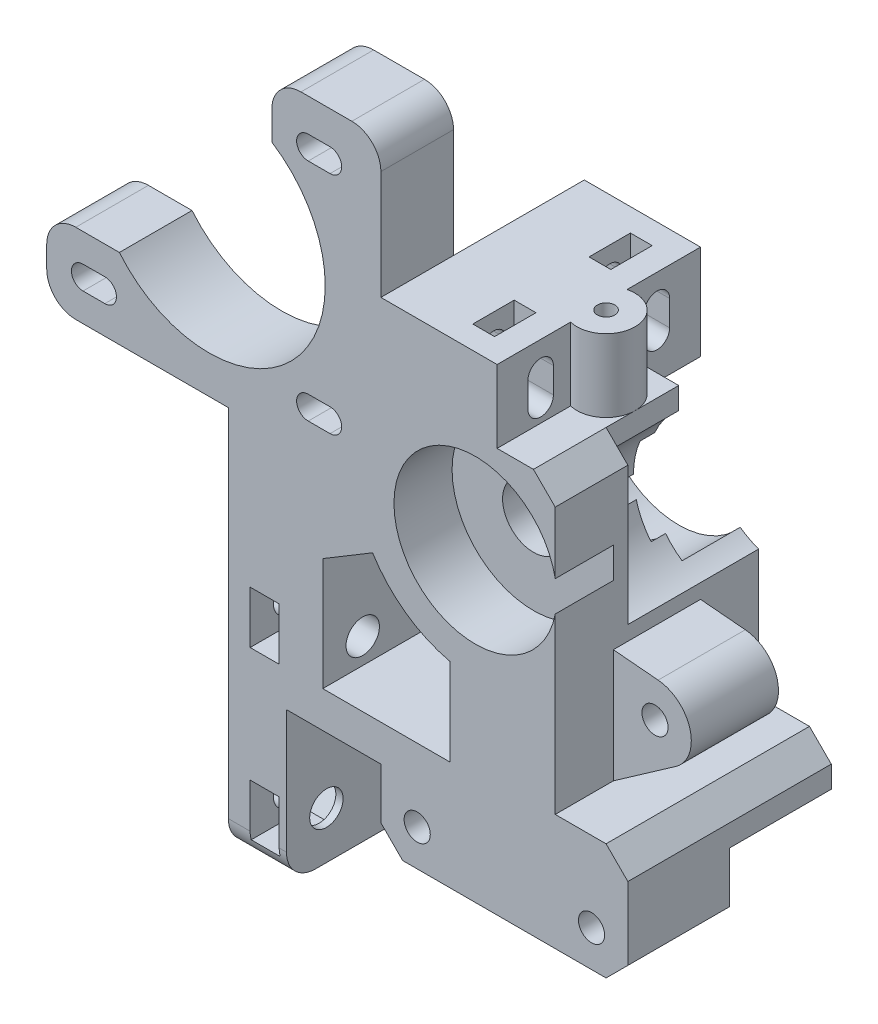
SolidWorks part; units mm, degrees
ref_plane "Front Plane" through (0, 0, 0) normal (0, 0, 1) x (1, 0, 0)
ref_plane "Top Plane" through (0, 0, 0) normal (0, 1, 0) x (1, 0, 0)
ref_plane "Right Plane" through (0, 0, 0) normal (1, 0, 0) x (0, 0, -1)
sketch "Sketch1" plane through (0, 0, 0) normal (0, 0, 1) x (1, 0, 0)
  line L0 (0, 0) -> (0, -11)
  line L1 (0, -11) -> (25, -11)
  line L2 (25, -11) -> (25, -64)
  line L3 (25, -64) -> (33, -64)
  line L4 (33, -64) -> (33, -43)
  line L5 (33, -43) -> (46, -43)
  line L6 (46, -43) -> (46, -53)
  line L7 (46, -53) -> (85, -53)
  line L8 (85, -53) -> (85, -43) construction
  line L9 (85, -43) -> (80, -43)
  line L10 (80, -43) -> (80, -37)
  line L11 (80, -37) -> (70, -37)
  line L12 (70, -37) -> (78.6011, -30.9774)
  line L13 (70, -37) -> (70, -21.361) construction
  line L14 (70, -21.361) -> (76.169, -21.9007)
  line L15 (70, -21.361) -> (70, 12.639)
  line L16 (70, 12.639) -> (46, 12.639)
  line L17 (46, 12.639) -> (46, 31.639)
  line L18 (46, 31.639) -> (31, 31.639)
  line L19 (31, 31.639) -> (31, 23.639)
  line L20 (0, 0) -> (10, 0)
  line L21 (38, -22.5) -> (38, -38)
  line L22 (38, -38) -> (55.5, -38)
  line L23 (55.5, -38) -> (55.5, -26)
  line L24 (38, -22.5) -> (44.8573, -18.3797)
  line L25 (85, -48) -> (46, -48) construction
  line L26 (25, -11) -> (59, -11) construction
  line L27 (5, -5.5) -> (8, -5.5) construction
  line L28 (5, -3.9) -> (8, -3.9)
  line L29 (5, -7.1) -> (8, -7.1)
  line L30 (36, -5.5) -> (39, -5.5) construction
  line L31 (36, -3.9) -> (39, -3.9)
  line L32 (36, -7.1) -> (39, -7.1)
  line L33 (36, 25.5) -> (39, 25.5) construction
  line L34 (36, 27.1) -> (39, 27.1)
  line L35 (36, 23.9) -> (39, 23.9)
  line L36 (5, -5.5) -> (36, -5.5) construction
  line L37 (36, -5.5) -> (36, 25.5) construction
  line L38 (5, -5.5) -> (0, -5.5) construction
  arc A0 (85, -53) -> (85, -43) centre (85, -48) ccw
  circle A1 centre (75.7332, -26.8817) radius 5
  arc A2 (10, 0) -> (31, 23.639) centre (22.3388, 10.186) ccw
  arc A3 (44.8573, -18.3797) -> (55.5, -26) centre (59.3127, -9.4331) ccw
  circle A4 centre (51, -48) radius 1.8
  circle A5 centre (75, -48) radius 1.8
  circle A6 centre (85, -48) radius 1.8
  circle A7 centre (75.7332, -26.8817) radius 1.8
  circle A8 centre (59, -11) radius 4.25
  arc A9 (5, -3.9) -> (5, -7.1) centre (5, -5.5) ccw
  arc A10 (8, -7.1) -> (8, -3.9) centre (8, -5.5) ccw
  arc A11 (36, -3.9) -> (36, -7.1) centre (36, -5.5) ccw
  arc A12 (39, -7.1) -> (39, -3.9) centre (39, -5.5) ccw
  arc A13 (36, 27.1) -> (36, 23.9) centre (36, 25.5) ccw
  arc A14 (39, 23.9) -> (39, 27.1) centre (39, 25.5) ccw
  point P45 (6.5, -5.5)
  point P50 (37.5, -5.5)
  point P57 (37.5, 25.5)
  dimension "D1" = 11
  dimension "D14" = 35
  dimension "D9" = 10
  dimension "D15" = 10
  dimension "D21" = 10
  dimension "D28" = 17
  dimension "D31" = 3.6
  dimension "D33" = 24
  dimension "D34" = 34
  dimension "D35" = 8.5
  dimension "D37" = 1.6
  dimension "D39" = 5
  dimension "D40" = 16
  dimension "D2" = 25
  dimension "D4" = 8
  dimension "D5" = 21
  dimension "D6" = 13
  dimension "D7" = 10
  dimension "D8" = 39
  dimension "D10" = 5
  dimension "D11" = 6
  dimension "D12" = 10
  dimension "D13" = 10.5
  dimension "D16" = 40
  dimension "D17" = 34
  dimension "D18" = 24
  dimension "D19" = 19
  dimension "D20" = 15
  dimension "D22" = 8
  dimension "D23" = 15.5
  dimension "D24" = 17.5
  dimension "D25" = 12
  dimension "D26" = 8
  dimension "D27" = 121
  dimension "D29" = 5
  dimension "D30" = 5
  dimension "D32" = 5
  dimension "D36" = 3
  dimension "D38" = 31
  dimension "D41" = 53
extrude "Boss-Extrude1" add sketch "Sketch1" against normal blind 34 contours A2 L20 L0 L1 L2 L3 L4 L5 L6 L7 A0 L9 L10 L11 L12 A1 L14 L15 L16 L17 L18 L19 A14 L35 A13 L34 A12 L32 A11 L31 A10 L29 A9 L28 A8 A6 A5 A4 L24 A3 L23 L22 L21 | A1 A7 region at (48.0686, -19.084, 0) region at (79.3153, -23.5993, 0)
sketch "Sketch7" plane through (0, 0, 0) normal (0, 0, 1) x (1, 0, 0)
  line L1 (70, -21.361) -> (80.7332, -21.361)
  line L2 (70, -21.361) -> (70, -37)
  line L3 (70, -37) -> (80.7332, -37)
  line L4 (80.7332, -21.361) -> (80.7332, -37)
  circle A0 centre (59, -11) radius 11.2
  arc A1 (78.6011, -30.9774) -> (76.169, -21.9007) centre (75.7332, -26.8817) ccw construction
  dimension "D1" = 22.4
extrude "Cut-Extrude5" cut sketch "Sketch7" against normal blind 8
sketch "Sketch2" plane through (25, 0, 0) normal (-1, 0, 0) x (0, 0, 1)
  line L0 (-28.5, -34.5) -> (-5.5, -34.5) construction
  line L1 (-5.5, -34.5) -> (-5.5, -57.5) construction
  line L2 (-5.5, -57.5) -> (-28.5, -57.5) construction
  line L3 (-28.5, -57.5) -> (-28.5, -34.5) construction
  line L4 (-17, -57.5) -> (-17, -64) construction
  line L5 (-34, -64) -> (0, -64) construction
  line L6 (-34, -24) -> (-28, -24)
  line L7 (-34, -11) -> (-34, -64) construction
  line L8 (-28, -24) -> (-28, 13.5)
  line L9 (-28, 13.5) -> (-10, 13.5)
  line L10 (-10, 13.5) -> (-10, 31.639)
  line L11 (-34, 31.639) -> (0, 31.639) construction
  line L12 (-10, 31.639) -> (-34, 31.639)
  line L13 (-34, 31.639) -> (-34, -24)
  circle A0 centre (-28.5, -34.5) radius 2.3
  circle A1 centre (-5.5, -34.5) radius 2.3
  circle A2 centre (-5.5, -57.5) radius 2.3
  circle A3 centre (-28.5, -57.5) radius 2.3
  dimension "D3" = 4.6
  dimension "D1" = 23
  dimension "D2" = 6.5
  dimension "D4" = 6
  dimension "D5" = 37.5
  dimension "D6" = 18
  dimension "D7" = 40
extrude "Cut-Extrude1" cut sketch "Sketch2" against normal blind 28
sketch "Sketch4" plane through (0, 0, -34) normal (0, 0, -1) x (-1, 0, 0)
  line L0 (-25, -24) -> (-46, -11.3806)
  line L1 (-46, -11.3806) -> (-46, 31.639)
  line L2 (-46, 31.639) -> (0, 31.639)
  line L3 (0, 31.639) -> (0, -11)
  line L4 (0, -11) -> (-25, -11)
  line L5 (-25, -11) -> (-25, -24)
  line L6 (-70, 12.639) -> (-67, 12.639)
  line L7 (-46, -53) -> (-85, -53) construction
  line L8 (-70, 12.639) -> (-70, -19.361)
  line L9 (-70, -21.361) -> (-70, 12.639) construction
  line L10 (-80, -43) -> (-90, -43)
  line L11 (-67, 12.639) -> (-67, -0.361)
  line L12 (-80, -43) -> (-80, -53)
  line L13 (-80, -53) -> (-90, -53)
  line L14 (-90, -43) -> (-90, -53)
  arc A0 (-70, -19.361) -> (-67, -0.361) centre (-73.7732, -9.0284) ccw
  arc A1 (-85, -43) -> (-85, -53) centre (-85, -48) ccw construction
  dimension "D4" = 11
  dimension "D1" = 24.5
  dimension "D2" = 3
  dimension "D3" = 32
  dimension "D5" = 13
extrude "Cut-Extrude2" cut sketch "Sketch4" against normal blind 24
sketch "Sketch5" plane through (0, 0, -34) normal (0, 0, -1) x (-1, 0, 0)
  line L0 (-33, -24) -> (-33, -64)
  line L1 (-25, -24) -> (-38, -24) construction
  line L2 (-33, -24) -> (0, -24)
  line L3 (0, -24) -> (0, 31.639)
  line L4 (0, 31.639) -> (-90, 31.639)
  line L5 (-90, 31.639) -> (-90, -64)
  line L6 (-90, -64) -> (-33, -64)
  line L7 (-46, 31.639) -> (-31, 31.639) construction
  line L9 (-25, -64) -> (-33, -64) construction
  line L10 (-33, -64) -> (-33, -43) construction
  arc A0 (-85, -43) -> (-85, -53) centre (-85, -48) ccw construction
extrude "Cut-Extrude3" cut sketch "Sketch5" against normal blind 6 contours L5 L6 L0 L2 L3 L4
sketch "Sketch6" plane through (0, 0, -34) normal (0, 0, -1) x (-1, 0, 0)
  line L0 (-67, 12.639) -> (-67, -3.4502)
  line L1 (-70, -21.361) -> (-80.7332, -21.361)
  line L2 (-70, -21.361) -> (-70, -37)
  line L3 (-70, -37) -> (-80.7332, -37)
  line L4 (-80.7332, -21.361) -> (-80.7332, -37)
  line L5 (-67, -0.361) -> (-67, 12.639) construction
  line L6 (-67, 12.639) -> (-62, 12.639)
  line L7 (-46, 12.639) -> (-67, 12.639) construction
  line L8 (-62, 12.639) -> (-62, -0.417)
  circle A0 centre (-59, -11) radius 11
  arc A1 (-76.169, -21.9007) -> (-78.6011, -30.9774) centre (-75.7332, -26.8817) ccw construction
  dimension "D1" = 22
  dimension "D2" = 5
extrude "Cut-Extrude4" cut sketch "Sketch6" against normal blind 14 contours A0 L8 L6 L0 | A0 | L1 L4 L3 L2 region at (64.5868, 5.4811, -34) region at (59, -11, -34) region at (75.3666, -29.1805, -34)
sketch "Sketch8" plane through (0, 0, -28) normal (0, 0, -1) x (-1, 0, 0)
  line L1 (-46, -53) -> (-80, -53)
  line L2 (-46, -53) -> (-46, -43)
  line L3 (-46, -43) -> (-80, -43)
  line L4 (-80, -53) -> (-80, -43)
extrude "Cut-Extrude7" cut sketch "Sketch8" against normal blind 14
sketch "Sketch9" plane through (0, 0, -20) normal (0, 0, -1) x (-1, 0, 0)
  circle A0 centre (-59, -11) radius 7.9
  dimension "D1" = 15.8
extrude "Cut-Extrude8" cut sketch "Sketch9" against normal blind 2
sketch "Sketch10" plane through (0, 12.639, 0) normal (0, 1, 0) x (1, 0, 0)
  line L0 (70, 10) -> (70, 0)
  line L1 (70, 8) -> (70, 0) construction
  line L2 (57, 3.15) -> (57, 0) construction
  line L3 (55.5, 24.85) -> (58.5, 24.85)
  line L4 (55.5, 24.85) -> (55.5, 19.15)
  line L5 (55.5, 19.15) -> (58.5, 19.15)
  line L6 (58.5, 24.85) -> (58.5, 19.15)
  line L7 (55.5, 8.85) -> (58.5, 8.85)
  line L8 (55.5, 8.85) -> (55.5, 3.15)
  line L9 (55.5, 3.15) -> (58.5, 3.15)
  line L10 (58.5, 8.85) -> (58.5, 3.15)
  line L11 (57, 24.85) -> (57, 28) construction
  line L12 (57, 8.85) -> (57, 19.15) construction
  line L14 (70, 0) -> (46, 0) construction
  line L15 (70, 10) -> (67, 10)
  line L16 (67, 10) -> (67, 20)
  line L17 (67, 20) -> (62, 20)
  line L18 (67.4569, 20) -> (48, 20) construction
  line L19 (62, 20) -> (62, 17.873)
  line L20 (62, 17.873) -> (62, 10.127) construction
  line L21 (63, 14) -> (57, 14) construction
  line L22 (70, 0) -> (62, 0)
  line L23 (62, 0) -> (62, 10.127)
  line L24 (46, 28) -> (62, 28) construction
  arc A0 (62, 17.873) -> (62, 10.127) centre (63, 14) cw
  line M9 (67, 20) -> (62, 20)
  line M15 (70, 0) -> (70, 10)
  line M16 (70, 10) -> (67, 10)
  line M17 (67, 10) -> (67, 20)
  dimension "D5" = 4
  dimension "D2" = 5.7
  dimension "D3" = 3
  dimension "D4" = 3.15
  dimension "D6" = 5
extrude "Cut-Extrude9" cut sketch "Sketch10" against normal blind 10 contours L6 L3 L4 L5 | L19 A0 L16 M9 | A0 L23 L22 M17 M15 M16 | L8 L9 L10 L7 region at (64.9023, 12.639, -18.5143) region at (66.0025, 12.639, -5.245) region at (57, 12.639, -22)
sketch "Sketch11" plane through (0, -53, 0) normal (0, -1, 0) x (1, 0, 0)
  line L0 (46, -14) -> (80, -14) construction
  circle A0 centre (63, -14) radius 1.2
  dimension "D1" = 2.4
extrude "Cut-Extrude10" cut sketch "Sketch11" against normal through all both and the other way through all
sketch "Sketch12" plane through (0, -53, 0) normal (0, -1, 0) x (1, 0, 0)
  circle A0 centre (63, -14) radius 8.1
  dimension "D1" = 16.2
extrude "Cut-Extrude11" cut sketch "Sketch12" against normal up to surface (10 mm away) from offset 5.5 up to face at (55.5, -43, -14.15) offset against normal yes
sketch "Sketch13" plane through (0, -53, 0) normal (0, -1, 0) x (1, 0, 0)
  circle A0 centre (63, -14) radius 6.1
  dimension "D1" = 12.2
extrude "Cut-Extrude12" cut sketch "Sketch13" against normal up to surface (5.5 mm away) up to face at (63, -47.5, -11.675)
sketch "Sketch15" plane through (62, 0, 0) normal (1, 0, 0) x (0, 0, -1)
  line L0 (6, 8.639) -> (6, 5.139) construction
  line L1 (7.75, 8.639) -> (7.75, 5.139)
  line L2 (4.25, 8.639) -> (4.25, 5.139)
  line L3 (22, 8.639) -> (22, 5.139) construction
  line L4 (23.75, 8.639) -> (23.75, 5.139)
  line L5 (20.25, 8.639) -> (20.25, 5.139)
  line L6 (6, 6.889) -> (22, 6.889) construction
  line L7 (6, 8.639) -> (6, 12.639) construction
  line L9 (10, 12.639) -> (0, 12.639) construction
  line L10 (10, 12.639) -> (10, 2.639) construction
  arc A0 (7.75, 8.639) -> (4.25, 8.639) centre (6, 8.639) ccw
  arc A1 (4.25, 5.139) -> (7.75, 5.139) centre (6, 5.139) ccw
  arc A2 (23.75, 8.639) -> (20.25, 8.639) centre (22, 8.639) ccw
  arc A3 (20.25, 5.139) -> (23.75, 5.139) centre (22, 5.139) ccw
  point P2 (6, 6.889)
  point P11 (22, 6.889)
  dimension "D2" = 1.75
  dimension "D1" = 3.5
  dimension "D3" = 4
  dimension "D4" = 16
  dimension "D5" = 4
extrude "Cut-Extrude14" cut sketch "Sketch15" against normal up to surface (16 mm away) up to face at (46, 0.6292, -19)
ref_plane "Plane1" through (28, 0, 0) normal (-1, 0, 0) x (0, 0, 1)
sketch "Sketch16" plane through (28, 0, 0) normal (-1, 0, 0) x (0, 0, 1)
  line L0 (-30.5785, -53.9) -> (-34, -53.9)
  line L1 (-24.3431, -34.5) -> (-26.4215, -30.9)
  line L2 (-26.4215, -30.9) -> (-30.5785, -30.9)
  line L3 (-30.5785, -30.9) -> (-32.6569, -34.5)
  line L4 (-32.6569, -34.5) -> (-30.5785, -38.1)
  line L5 (-30.5785, -38.1) -> (-26.4215, -38.1)
  line L6 (-26.4215, -38.1) -> (-24.3431, -34.5)
  line L7 (-24.3431, -57.5) -> (-26.4215, -53.9)
  line L8 (-26.4215, -53.9) -> (-30.5785, -53.9)
  line L9 (-30.5785, -53.9) -> (-32.6569, -57.5)
  line L10 (-32.6569, -57.5) -> (-30.5785, -61.1)
  line L11 (-30.5785, -61.1) -> (-26.4215, -61.1)
  line L12 (-26.4215, -61.1) -> (-24.3431, -57.5)
  line L13 (-9.6569, -57.5) -> (-7.5785, -61.1)
  line L14 (-7.5785, -61.1) -> (-3.4215, -61.1)
  line L15 (-3.4215, -61.1) -> (-1.3431, -57.5)
  line L16 (-1.3431, -57.5) -> (-3.4215, -53.9)
  line L17 (-3.4215, -53.9) -> (-7.5785, -53.9)
  line L18 (-7.5785, -53.9) -> (-9.6569, -57.5)
  line L19 (-9.6569, -34.5) -> (-7.5785, -38.1)
  line L20 (-7.5785, -38.1) -> (-3.4215, -38.1)
  line L21 (-3.4215, -38.1) -> (-1.3431, -34.5)
  line L22 (-1.3431, -34.5) -> (-3.4215, -30.9)
  line L23 (-3.4215, -30.9) -> (-7.5785, -30.9)
  line L24 (-7.5785, -30.9) -> (-9.6569, -34.5)
  line L25 (-34, -24) -> (-34, -64) construction
  line L26 (-34, -53.9) -> (-34, -61.1)
  line L27 (-34, -61.1) -> (-30.5785, -61.1)
  line L28 (-30.5785, -30.9) -> (-34, -30.9)
  line L29 (-34, -30.9) -> (-34, -38.1)
  line L30 (-34, -38.1) -> (-30.5785, -38.1)
  line L31 (-3.4215, -30.9) -> (0, -30.9)
  line L32 (0, -11) -> (0, -64) construction
  line L33 (0, -30.9) -> (0, -38.1)
  line L34 (0, -38.1) -> (-3.4215, -38.1)
  line L35 (-3.4215, -53.9) -> (0, -53.9)
  line L36 (0, -53.9) -> (0, -61.1)
  line L37 (0, -61.1) -> (-3.4215, -61.1)
  circle A0 centre (-28.5, -34.5) radius 3.6 construction
  circle A1 centre (-28.5, -57.5) radius 3.6 construction
  circle A2 centre (-5.5, -57.5) radius 3.6 construction
  circle A3 centre (-5.5, -34.5) radius 3.6 construction
  dimension "D1" = 7.2
extrude "Cut-Extrude15" cut sketch "Sketch16" against normal blind 4 contours L29 L30 L4 L3 L28 | L5 L6 L1 L2 L3 L4 | L26 L27 L10 L9 L0 | L11 L12 L7 L8 L9 L10 | L23 L24 L19 L20 L21 L22 | L34 L33 L31 L22 L21 | L17 L18 L13 L14 L15 L16 | L37 L36 L35 L16 L15 region at (28, -57.5, -32.7333) region at (28, -57.5, -28.5) region at (28, -34.5, -28.5) region at (28, -34.5, -32.7333) region at (28, -57.5, -5.5) region at (28, -57.5, -1.2667) region at (28, -34.5, -5.5) region at (28, -34.5, -1.2667)
fillet "Fillet1" radius 4 7 edges at (31, 31.639, -5) (46, 31.639, -5) (0, 0, -5) (0, -11, -5) (29, -24, -34) (29, -64, -34) (29, -64, 0)
sketch "Sketch17" plane through (0, 0, -10) normal (0, 0, -1) x (-1, 0, 0)
  line L0 (-80, -43) -> (-85, -43) construction
  line L1 (-80, -53) -> (-90, -53)
  line L2 (-80, -53) -> (-80, -43)
  line L3 (-80, -43) -> (-90, -43)
  line L4 (-90, -53) -> (-90, -43)
  arc A0 (-85, -43) -> (-85, -53) centre (-85, -48) ccw construction
extrude "fail" cut sketch "Sketch17" against normal through all both and the other way through all
chamfer "Chamfer1" distance 3 angle 45 4 edges at (46, -53, -7) (80, -53, -7) (70, 2.639, -5) (80, -37, -14)
